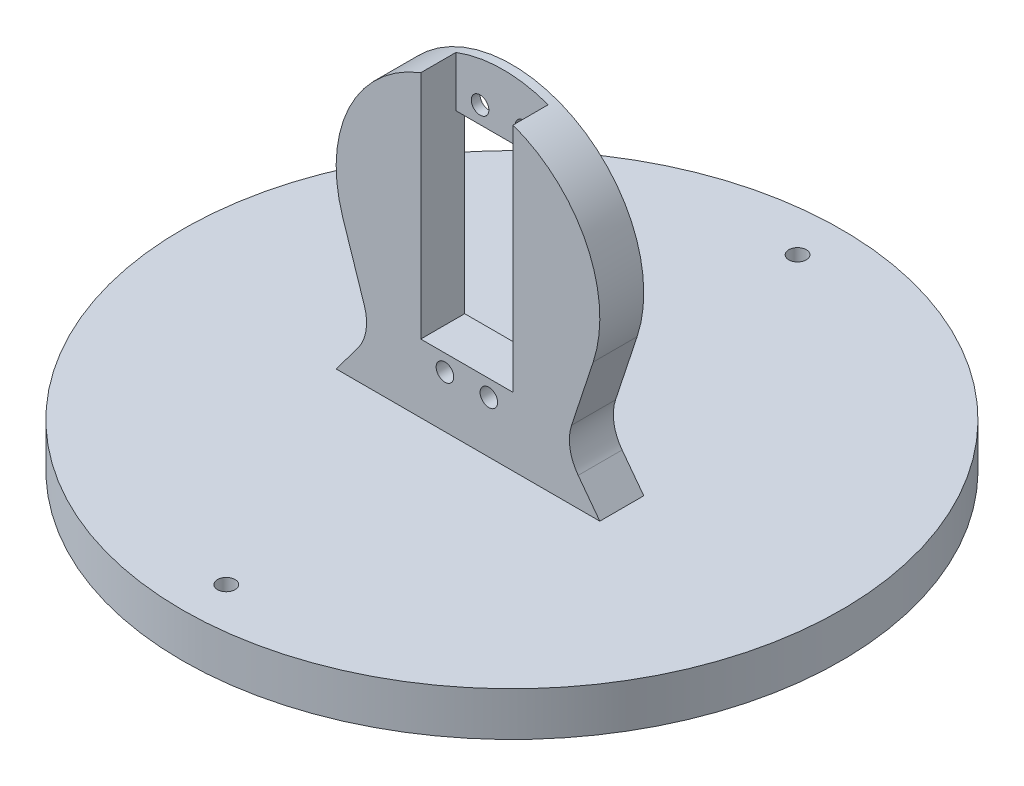
SolidWorks part; units mm, degrees
ref_plane "Plan de face" through (0, 0, 0) normal (0, 0, 1) x (1, 0, 0)
ref_plane "Plan de dessus" through (0, 0, 0) normal (0, 1, 0) x (1, 0, 0)
ref_plane "Plan de droite" through (0, 0, 0) normal (1, 0, 0) x (0, 0, -1)
sketch "Esquisse1" plane through (0, 0, 0) normal (0, 1, 0) x (1, 0, 0)
  circle A0 centre (0, 0) radius 75
  circle A1 centre (0, 0) radius 65 construction
  circle A2 centre (0, 65) radius 2
  circle A3 centre (0, -65) radius 2
  point P11 (0, 0)
  dimension "D1" = 150
  dimension "D3" = 4
  dimension "D2" = 10
  dimension "D4" = 2
extrude "Boss.-Extru.1" add sketch "Esquisse1" along normal blind 10
sketch "Esquisse2" plane through (0, 0, 0) normal (0, 0, 1) x (1, 0, 0)
  line L0 (2, 10) -> (-2, 10) construction
  line L1 (28.4916, 40.6068) -> (23.5768, 25.6991)
  line L2 (25.0739, 16.5681) -> (30, 10)
  line L3 (75, 10) -> (-75, 10) construction
  line L4 (0, 50) -> (0, 0) construction
  line L5 (-25.0739, 16.5681) -> (-30, 10)
  line L6 (-28.4916, 40.6068) -> (-23.5768, 25.6991)
  line L7 (-30, 10) -> (30, 10)
  line L8 (-0.2487, 73.3654) -> (-0.2487, 25.5154) construction
  line L9 (-10.7487, 73.3654) -> (10.2513, 73.3654)
  line L10 (-10.7487, 25.5154) -> (10.2513, 25.5154)
  line L11 (-10.7487, 56.2154) -> (10.2513, 56.2154) construction
  line L12 (-10.7487, 66.5154) -> (10.2513, 66.5154)
  line L13 (-5.2487, 21.7647) -> (-5.2487, 70.3947) construction
  line L14 (-10.7487, 25.5154) -> (10.2513, 25.5154)
  line L15 (-10.7487, 25.5154) -> (-10.7487, 18.6654) construction
  line L16 (-10.7487, 18.6654) -> (10.2513, 18.6654)
  line L17 (10.2513, 25.5154) -> (10.2513, 18.6654)
  line L18 (-10.7487, 70.3947) -> (10.2513, 70.3947) construction
  line L19 (-5.2487, 21.7647) -> (-10.7487, 21.7647) construction
  line L20 (-5.2487, 21.7647) -> (10.2513, 21.7647) construction
  line L21 (-10.7487, 70.3947) -> (10.2513, 21.7647) construction
  line L22 (-10.7487, 21.7647) -> (10.2513, 70.3947) construction
  line L23 (-0.2487, 46.0797) -> (-10.7487, 46.0797) construction
  line L24 (-0.2487, 25.5154) -> (-0.2487, 18.6654) construction
  line L25 (-10.7487, 66.5154) -> (-10.7487, 25.5154)
  line L26 (-10.7487, 73.3654) -> (-10.7487, 66.5154)
  line L27 (10.2513, 66.5154) -> (10.2513, 25.5154)
  line L28 (10.2513, 73.3654) -> (10.2513, 66.5154)
  line L29 (-10.7487, 73.3654) -> (-10.7487, 78.0083)
  line L30 (10.2513, 73.3654) -> (10.2513, 78.1942)
  arc A0 (28.4916, 40.6068) -> (-28.4916, 40.6068) centre (0, 50) ccw
  arc A1 (23.5768, 25.6991) -> (25.0739, 16.5681) centre (33.0739, 22.5681) ccw
  arc A2 (-25.0739, 16.5681) -> (-23.5768, 25.6991) centre (-33.0739, 22.5681) ccw
  circle A3 centre (-5.2487, 70.3947) radius 2
  circle A4 centre (-5.2487, 21.7647) radius 2
  circle A5 centre (4.7513, 21.7647) radius 2
  circle A6 centre (4.7513, 70.3947) radius 2
  point P17 (21.9428, 20.743)
  point P20 (-21.9428, 20.743)
  dimension "D1" = 60
  dimension "D3" = 10
  dimension "D10" = 4
  dimension "D11" = 4
  dimension "D2" = 40
  dimension "D4" = 60
  dimension "D5" = 15.697
  dimension "D6" = 17.15
  dimension "D7" = 6.85
  dimension "D8" = 41
  dimension "D9" = 6.85
  dimension "D12" = 48.63
  dimension "D13" = 21
  dimension "D14" = 5
extrude "Boss.-Extru.2" add sketch "Esquisse2" along normal blind 2 contours A2 L5 L7 L2 A1 L1 A0 L6 A5 A4 A3 L12 L27 L10 L25 A6 | L28 L9 L26 L12 A3 A6 | L30 A0 L29 L9 region at (25.1715, 33.4374, 0) region at (-0.196, 76.3966, 0) region at (-0.2487, 69.8443, 0)
extrude "Boss.-Extru.5" add sketch "Esquisse2<7>" along normal blind 8 from surface contours A2 L5 L7 L2 A1 L1 A0 L6 L9 L28 L27 L10 L25 L26 A4 A5 region at (25.1715, 33.4374, 0) starting at face at (0, 28.0968, 2)
sketch "Esquisse2<7>" plane through (0, 0, 0) normal (0, 0, 1) x (1, 0, 0) same geometry as "Esquisse2"
